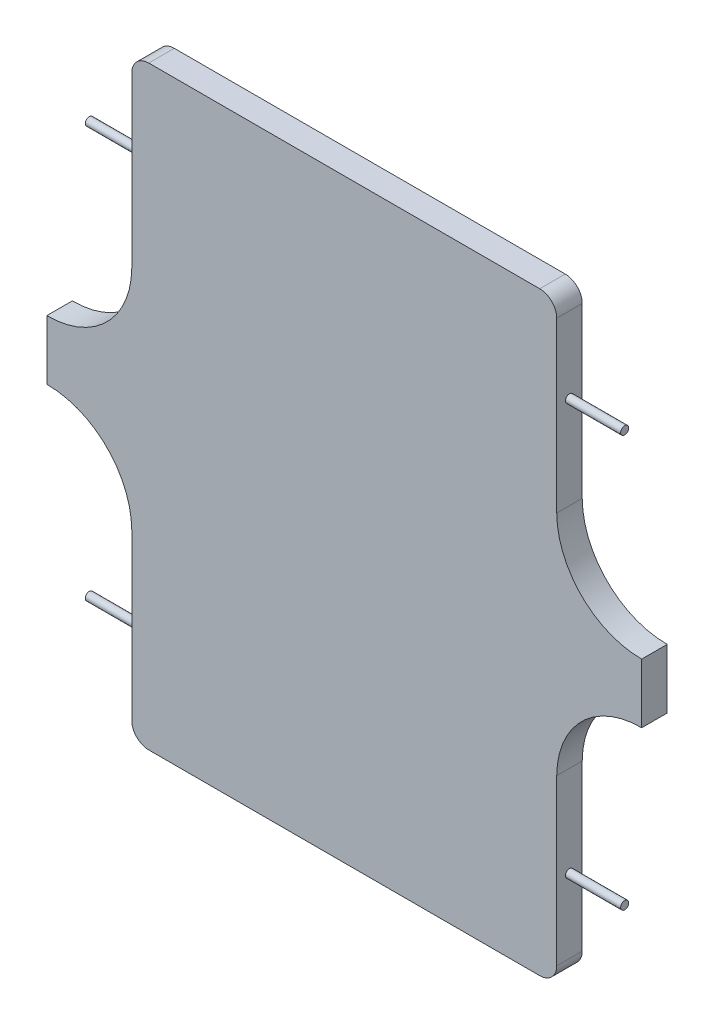
SolidWorks part; units mm, degrees
note: The reader was unsure of these and kept them because the rebuilt part matched: shared geometry of "Schizzo3D1<5>".
ref_plane "Piano frontale" through (0, 0, 0) normal (0, 0, 1) x (1, 0, 0)
ref_plane "Piano superiore" through (0, 0, 0) normal (0, 1, 0) x (1, 0, 0)
ref_plane "Piano destro" through (0, 0, 0) normal (1, 0, 0) x (0, 0, -1)
sketch "Schizzo1" plane through (0, 0, 0) normal (0, 0, 1) x (1, 0, 0)
  line L0 (-49.4685, 22.2576) -> (450.5315, 22.2576)
  line L3 (-49.4685, -677.7424) -> (450.5315, -677.7424)
  line L4 (200.5315, 22.2576) -> (200.5315, -677.7424) construction
  line L15 (-149.4685, -365.1174) -> (-149.4685, -295.1174)
  line L20 (550.5315, -365.1174) -> (550.5315, -295.1174)
  line L28 (450.5315, 22.2576) -> (450.5315, -196.3049)
  line L29 (-49.4685, 22.2576) -> (-49.4685, -196.3049)
  line L34 (-49.4685, -463.9299) -> (-49.4685, -677.7424)
  line L35 (450.5315, -463.9299) -> (450.5315, -677.7424)
  arc A0 (-49.4685, -196.3049) -> (-149.4685, -295.1174) centre (-148.8748, -195.7112) cw
  arc A1 (-49.4685, -463.9299) -> (-149.4685, -365.1174) centre (-148.8748, -464.5237) ccw
  arc A2 (450.5315, -463.9299) -> (550.5315, -365.1174) centre (549.9377, -464.5237) cw
  arc A3 (450.5315, -196.3049) -> (550.5315, -295.1174) centre (549.9377, -195.7112) ccw
  point P10 (0, 0)
  point P11 (0, 0)
  dimension "D1" = 700
  dimension "D2" = 500
  dimension "D3" = 70
extrude "Estrusione-Estrusione2" add sketch "Schizzo1" along normal blind 30
sketch3d "Schizzo3D1"
  circle A1 centre (515.5315, -87.0237, 15) radius 4.75
  circle A2 centre (-114.4685, -87.0237, 15) radius 4.75
  circle A3 centre (-114.4685, -570.8362, 15) radius 4.75
  circle A4 centre (515.5315, -570.8362, 15) radius 4.75
  point P2 (520.2815, -87.0237, 15)
  point P12 (-109.7185, -87.0237, 15)
  point P15 (-109.7185, -570.8362, 15)
  point P18 (520.2815, -570.8362, 15)
  dimension "D1" = 9.5
extrude "Estrusione-Estrusione7" add sketch "Schizzo3D1" along direction (1, 0, 0) on the side against the normal blind 65 contours A2 | A3
extrude "Estrusione-Estrusione8" add sketch "Schizzo3D1<5>" along direction (1, 0, 0) on the side of the normal blind 65 contours A1 | A4
sketch3d "Schizzo3D1<5>" same geometry as "Schizzo3D1"
fillet "Raccordo3" radius 20 1 edges at (-49.4685, 22.2576, 15)
fillet "Raccordo4" radius 20 1 edges at (450.5315, 22.2576, 15)
fillet "Raccordo5" radius 20 1 edges at (450.5315, -677.7424, 15)
fillet "Raccordo6" radius 20 1 edges at (-49.4685, -677.7424, 15)
